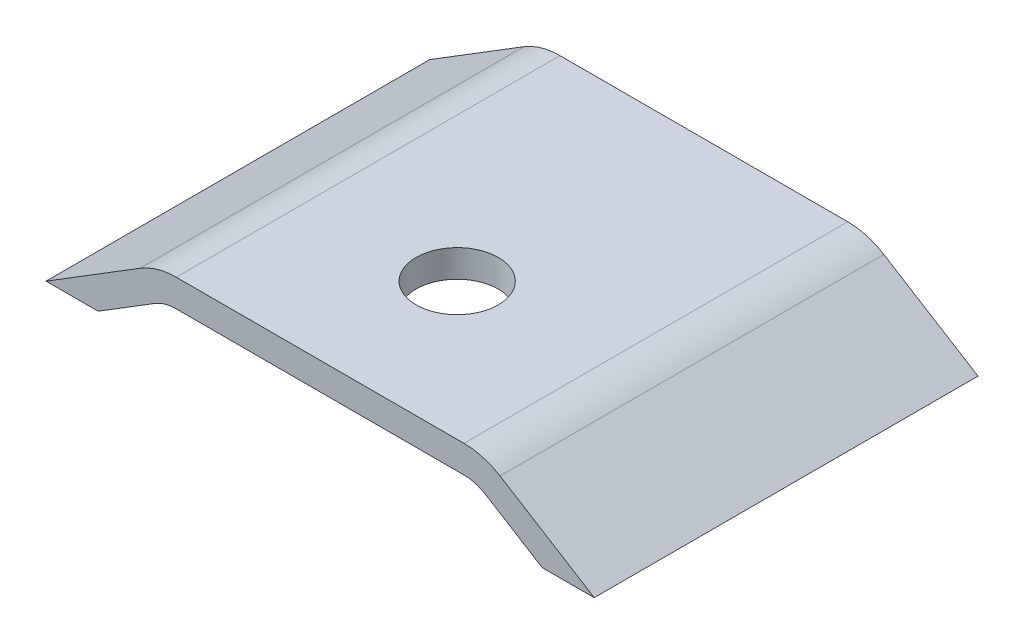
SolidWorks part; units mm, degrees
ref_plane "Front Plane" through (0, 0, 0) normal (0, 0, 1) x (1, 0, 0)
ref_plane "Top Plane" through (0, 0, 0) normal (0, 1, 0) x (1, 0, 0)
ref_plane "Right Plane" through (0, 0, 0) normal (1, 0, 0) x (0, 0, -1)
sketch "Sketch1" plane through (0, 0, 0) normal (0, 0, 1) x (1, 0, 0)
  line L0 (-50.8, -6.35) -> (-30.2744, 6.35)
  line L1 (50.8, -6.35) -> (-50.8, -6.35) construction
  line L2 (50.8, -6.35) -> (50.8, 6.35) construction
  line L3 (50.8, 6.35) -> (-50.8, 6.35) construction
  line L4 (-50.8, -6.35) -> (-50.8, 6.35) construction
  line L5 (50.8, -6.35) -> (-50.8, 6.35) construction
  line L6 (50.8, 6.35) -> (-50.8, -6.35) construction
  line L7 (-30.2744, 6.35) -> (30.2744, 6.35)
  line L8 (30.2744, 6.35) -> (50.8, -6.35)
  line L9 (50.8, -6.35) -> (-50.8, -6.35)
  point P0 (0, 0)
  point P6 (-23.3352, 6.35)
  point P9 (-30.2744, 6.35)
  dimension "D1" = 101.6
  dimension "D2" = 12.7
  dimension "D3" = 148.253
extrude "Boss-Extrude1" add sketch "Sketch1" along normal blind 71.12
fillet "Fillet1" radius 12.7 2 edges at (-30.2744, 6.35, 35.56) (30.2744, 6.35, 35.56)
sketch "Sketch3" plane through (0, 0, 71.12) normal (0, 0, 1) x (1, 0, 0)
  line L27 (-48.1271, -10.6699) -> (48.1271, -10.6699)
  line L30 (48.1271, -10.6699) -> (30.6725, 0.1299)
  line L31 (26.6631, 1.27) -> (-26.6631, 1.27)
  line L32 (-30.6725, 0.1299) -> (-48.1271, -10.6699)
  line L33 (48.1271, -10.6699) -> (30.6725, 0.1299)
  line L34 (26.6631, 1.27) -> (-26.6631, 1.27)
  line L35 (-30.6725, 0.1299) -> (-48.1271, -10.6699)
  arc A17 (30.6725, 0.1299) -> (26.6631, 1.27) centre (26.6631, -6.35) ccw
  arc A18 (-26.6631, 1.27) -> (-30.6725, 0.1299) centre (-26.6631, -6.35) ccw
  arc A19 (30.6725, 0.1299) -> (26.6631, 1.27) centre (26.6631, -6.35) ccw
  arc A20 (-26.6631, 1.27) -> (-30.6725, 0.1299) centre (-26.6631, -6.35) ccw
  dimension "D1" = 5.08
extrude "Cut-Extrude1" cut sketch "Sketch3" against normal up to next
ref_plane "Plane1" through (0, 0, 35.56) normal (0, 0, -1) x (-1, 0, 0)
sketch "Sketch4" plane through (0, 0, 0) normal (0, 1, 0) x (1, 0, 0)
  circle A0 centre (-52.8588, -9.8061) radius 3.0953
sketch "Sketch5" plane through (0, 6.35, 0) normal (0, 1, 0) x (1, 0, 0)
  line L0 (26.6631, -71.12) -> (-26.6631, -71.12) construction
  circle A0 centre (0, -45.72) radius 7.62
  dimension "D1" = 15.24
  dimension "D2" = 25.4
extrude "Cut-Extrude2" cut sketch "Sketch5" against normal up to next
